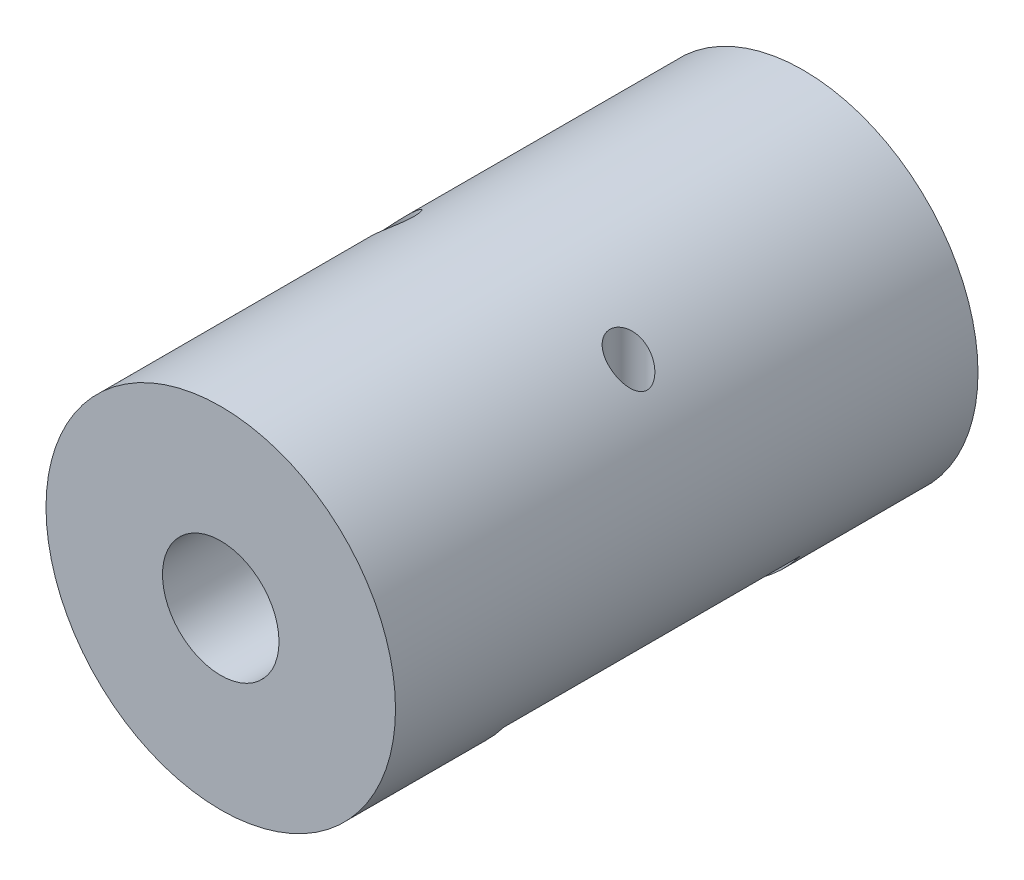
SolidWorks part; units mm, degrees
material "Delrin 2700 NC010, Low Viscosity Acetal Copolymer (SS)"
ref_plane "Front Plane" through (0, 0, 0) normal (0, 0, 1) x (1, 0, 0)
ref_plane "Top Plane" through (0, 0, 0) normal (0, 1, 0) x (1, 0, 0)
ref_plane "Right Plane" through (0, 0, 0) normal (1, 0, 0) x (0, 0, -1)
sketch "Sketch1" plane through (0, 0, 0) normal (0, 1, 0) x (1, 0, 0)
  line L0 (0, -25) -> (0, 25) construction
  line L1 (15, -25) -> (5, -25)
  line L2 (15, -25) -> (15, 25)
  line L3 (15, 25) -> (5, 25)
  line L4 (5, -25) -> (5, 25)
  line L5 (0, 25) -> (5, 25) construction
  line L6 (5, -25) -> (0, -25) construction
  line L7 (0, 0) -> (5, 0) construction
  dimension "D1" = 10
  dimension "D2" = 30
  dimension "D3" = 50
revolve "Revolve1" add sketch "Sketch1" angle 360 about L0
cosmetic thread "Cosmetic Thread1" parameters "D2"=12
sketch "Sketch2" plane through (0, 0, 0) normal (0, 0, 1) x (1, 0, 0)
  line L0 (-13.4075, 0) -> (27.2995, 0) construction
  line L1 (-15, 15) -> (15, 15) construction
  line L2 (-15, 15) -> (-15, 9) construction
  line L3 (-15, 9) -> (15, 9) construction
  line L4 (15, 15) -> (15, 9) construction
  line L5 (-15, -15) -> (15, -15)
  line L6 (-15, -15) -> (-15, -9)
  line L7 (-15, -9) -> (15, -9)
  line L8 (15, -15) -> (15, -9)
  line L9 (-6, 9) -> (-6, -9) construction
  line L10 (6, 9) -> (6, -9) construction
  line L11 (0, 0) -> (0, 9) construction
  line L12 (8.2995, 9) -> (8.2995, -9) construction
  line L13 (11.2995, -9) -> (11.2995, 9) construction
  circle A0 centre (0, 0) radius 15 construction
  dimension "D1" = 12
  dimension "D2" = 3
  dimension "D3" = 18
extrude "Cut-Extrude1" cut sketch "Sketch2" against normal blind 12.7 and the other way blind 12.7
sketch "Sketch3" plane through (0, 0, 0) normal (0, 0, 1) x (1, 0, 0)
  line L0 (10, -9) -> (10, -19.0464) construction
  line L1 (10, 12.4274) -> (8.4, 12.4274)
  line L2 (10, 12.4274) -> (10, -9)
  line L3 (10, -9) -> (8.4, -9)
  line L4 (8.4, 12.4274) -> (8.4, -9)
  line L5 (-10, -9) -> (-10, -14.3538) construction
  line L6 (-10, 12.4274) -> (-8.4, 12.4274)
  line L7 (-10, 12.4274) -> (-10, -9)
  line L8 (-10, -9) -> (-8.4, -9)
  line L9 (-8.4, 12.4274) -> (-8.4, -9)
  line L10 (0, 0) -> (0, 11.1925) construction
  line L11 (0, 0) -> (20.8751, 0) construction
  line L13 (12, -9) -> (-12, -9) construction
  line L14 (10, 12.4274) -> (11.6, 12.4274) construction
  line L15 (11.6, 12.4274) -> (11.6, -9) construction
  line L16 (11.6, -9) -> (10, -9) construction
  line L17 (-10, -9) -> (-11.6, -9) construction
  line L18 (-11.6, -9) -> (-11.6, 12.4274) construction
  line L19 (-11.6, 12.4274) -> (-10, 12.4274) construction
  circle A0 centre (0, 0) radius 15 construction
  dimension "D1" = 20
  dimension "D2" = 3.2
revolve "Cut-Revolve1" cut sketch "Sketch3" angle 360 about L0
revolve "Cut-Revolve2" cut sketch "Sketch3<3>" angle 360 about L5
sketch "Sketch3<3>" plane through (0, 0, 0) normal (0, 0, 1) x (1, 0, 0) same geometry as "Sketch3"
